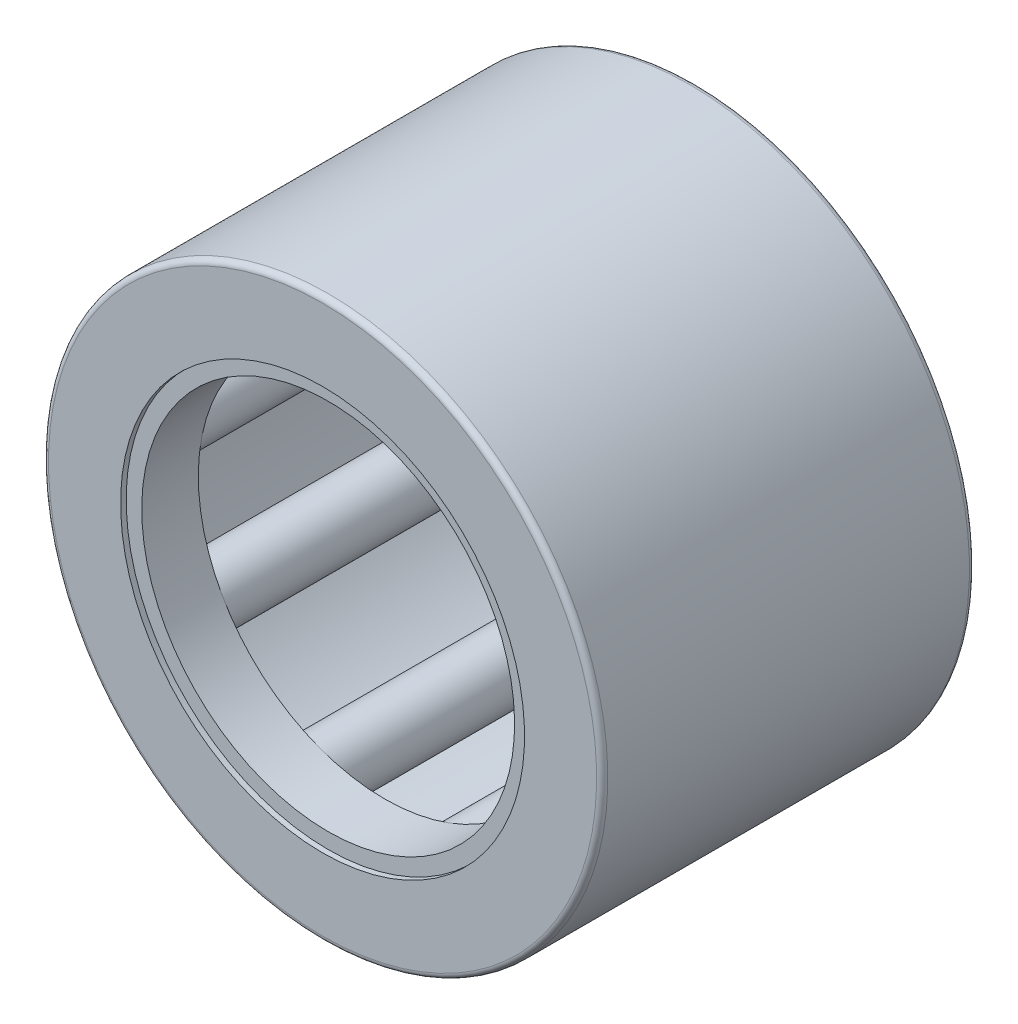
SolidWorks part; units mm, degrees
note: '?' marks a value the reader was unsure of.
ref_plane "Front Plane" through (0, 0, 0) normal (0, 0, 1) x (1, 0, 0)
ref_plane "Top Plane" through (0, 0, 0) normal (0, 1, 0) x (1, 0, 0)
ref_plane "Right Plane" through (0, 0, 0) normal (1, 0, 0) x (0, 0, -1)
sketch "Sketch1" plane through (0, 0, 0) normal (1, 0, 0) x (0, 0, -1)
  line L0 (-4, 0) -> (4, 0) construction
  line L1 (0, 0) -> (0, 6) construction
  line L2 (-4, 0) -> (-4, 6) construction
  line L3 (-4, 6) -> (4, 6)
  line L4 (4, 6) -> (4, 0) construction
  line L5 (4, 0) -> (3.3333, 0) construction
  line L6 (3.3333, 0) -> (3.3333, 5.3333) construction
  line L7 (3.3333, 5.3333) -> (-3.3333, 5.3333)
  line L8 (-3.3333, 5.3333) -> (-3.3333, 0) construction
  line L9 (-3.3333, 0) -> (-4, 0) construction
  line L10 (-4, 6) -> (-4, 4.3333)
  line L11 (-4, 4.3333) -> (-3.3333, 4.3333)
  line L12 (-3.3333, 4.3333) -> (-3.3333, 5.3333)
  line L13 (3.3333, 6) -> (3.3333, 5.3333) construction
  line L14 (3.3333, 5.3333) -> (3.3333, 4.3333)
  line L15 (3.3333, 4.3333) -> (4, 4.3333)
  line L16 (4, 4.3333) -> (4, 6)
  line L17 (3.3333, 5.3333) -> (3.3333, 4.6667) construction
  line L18 (3.3333, 4.6667) -> (3.3333, 4) construction
  line L19 (3.3333, -5.3333) -> (3.3333, -4.6667) construction
  line L20 (3.3333, -6) -> (3.3333, -5.3333) construction
  line L21 (4, -4.3333) -> (4, -6) construction
  line L22 (3.3333, -4.3333) -> (4, -4.3333) construction
  line L23 (3.3333, -5.3333) -> (3.3333, -4.3333) construction
  line L24 (-3.3333, -4.3333) -> (-3.3333, -5.3333) construction
  line L25 (-4, -4.3333) -> (-3.3333, -4.3333) construction
  line L26 (-4, -6) -> (-4, -4.3333) construction
  line L27 (3.3333, -5.3333) -> (-3.3333, -5.3333) construction
  line L28 (-4, -6) -> (4, -6) construction
  point P4 (0, 4)
  dimension "C | Width" = 8
  dimension "Fw | ID" = 8
  dimension "D | OD" = 12
sketch "Sketch7" plane through (0, 0, 0) normal (1, 0, 0) x (0, 0, -1)
  line L0 (-4, 6) -> (-4, 4.3333) construction
  line L1 (-4, 4.3333) -> (-3.3333, 4.3333) construction
  line L2 (-3.3333, 4.3333) -> (-3.3333, 5.3333) construction
  line L3 (3.3333, 5.3333) -> (-3.3333, 5.3333) construction
  line L4 (3.3333, 5.3333) -> (3.3333, 4.3333) construction
  line L5 (3.3333, 4.3333) -> (4, 4.3333) construction
  line L6 (4, 4.3333) -> (4, 6) construction
  line L8 (-4, 6) -> (4, 6) construction
  line L9 (-4, 6) -> (-4, 4.3333)
  line L10 (-4, 4.3333) -> (-3.3333, 4.3333)
  line L13 (-3.3333, 4.3333) -> (-3.3333, 5.3333)
  line L16 (3.3333, 5.3333) -> (-3.3333, 5.3333)
  line L17 (3.3333, 5.3333) -> (3.3333, 4.3333)
  line L18 (3.3333, 4.3333) -> (4, 4.3333)
  line L19 (4, 4.3333) -> (4, 6)
  line L20 (-4, 6) -> (4, 6)
revolve "Revolve1" add sketch "Sketch7" angle 360 about L0
sketch "Sketch2" plane through (0, 0, 0) normal (1, 0, 0) x (0, 0, -1)
  line L0 (-4, 4.3333) -> (-3.3333, 4.3333) construction
  line L1 (-2.6667, 4.6667) -> (2.6667, 4.6667) construction
  line L2 (-2.6667, 4.6667) -> (-2.6667, 5.3333) construction
  line L3 (-2.6667, 5.3333) -> (2.6667, 5.3333)
  line L4 (2.6667, 4.6667) -> (2.6667, 5.3333) construction
  line L5 (3.3333, 4.3333) -> (4, 4.3333) construction
  line L6 (-3.3333, 4.6667) -> (-2.6667, 4.6667) construction
  line L7 (2.6667, 4.6667) -> (3.3333, 4.6667) construction
  line L8 (4, 6) -> (4, 0) construction
  line L9 (-2.6667, 4.8333) -> (-2.6667, 4.5) construction
  line L10 (-3.3333, 4.6667) -> (-3.3333, 4.3333) construction
  line L11 (-2.6667, 5.3333) -> (-2.6667, 4.8333)
  line L12 (2.6667, 5.3333) -> (2.6667, 4.8333)
  line L13 (2.6667, 4.8333) -> (-2.6667, 4.8333)
  line L14 (0, 5.3333) -> (0, 4) construction
  line L16 (-2.6667, 4.5) -> (-3.3333, 4.5) construction
  line L17 (0, 0) -> (4, 0) construction
  line L18 (-2.6667, -4.5) -> (-3.3333, -4.5) construction
  line L19 (0, -5.3333) -> (0, -4) construction
  line L20 (-3.3333, -4.6667) -> (-3.3333, -4.3333) construction
  line L21 (-2.6667, -4.8333) -> (-2.6667, -4.5) construction
  line L22 (2.6667, -4.6667) -> (3.3333, -4.6667) construction
  line L23 (-3.3333, -4.6667) -> (-2.6667, -4.6667) construction
  line L24 (2.6667, -4.6667) -> (2.6667, -5.3333) construction
  line L25 (-2.6667, -4.6667) -> (-2.6667, -5.3333) construction
  line L26 (-2.6667, -4.6667) -> (2.6667, -4.6667) construction
  line L27 (2.6667, -4.8333) -> (-2.6667, -4.8333) construction
  line L28 (2.6667, -5.3333) -> (2.6667, -4.8333) construction
  line L29 (-2.6667, -5.3333) -> (-2.6667, -4.8333) construction
  line L30 (-2.6667, -5.3333) -> (2.6667, -5.3333) construction
  line L33 (3.3333, 5.3333) -> (-3.3333, 5.3333) construction
  line L34 (3.3333, 5.3333) -> (3.3333, 4.3333) construction
  line L35 (-3.3333, 4.3333) -> (-3.3333, 5.3333) construction
  line L36 (0, 0) -> (0, 6) construction
  point P16 (0, 4.6667)
revolve "Revolve2" add sketch "Sketch2" angle 360 about L1
sketch "Sketch3" plane through (0, 0, 0) normal (1, 0, 0) x (0, 0, -1)
  line L1 (-3.3333, 4.6667) -> (3.3333, 4.6667)
  line L2 (-3.3333, 4.6667) -> (-3.3333, 4.8333)
  line L3 (-3.3333, 4.8333) -> (3.3333, 4.8333)
  line L4 (3.3333, 4.6667) -> (3.3333, 4.8333)
  line L5 (0, 0) -> (4, 0) construction
  line L7 (3.3333, -4.6667) -> (3.3333, -4.8333) construction
  line L8 (-3.3333, -4.8333) -> (3.3333, -4.8333) construction
  line L9 (-3.3333, -4.6667) -> (-3.3333, -4.8333) construction
  line L10 (-3.3333, -4.6667) -> (3.3333, -4.6667) construction
  line L11 (3.3333, 5.3333) -> (3.3333, 4.3333) construction
  line L12 (4, 6) -> (4, 0) construction
revolve "Revolve3" add sketch "Sketch3" angle 360 about L1
ref_axis "Axis1" through (0, 4.3333, 4) along (0, 1, 0)?
pattern_circular "CirPattern1" count 9 every 40 about axis through (0, 0, 4) along (0, 0, -1) of bodies 166 167
fillet "Fillet1" radius 0.12 2 edges at (0, -6, -4) (0, -6, 4)
sketch "Sketch4" plane through (0, 0, 0) normal (1, 0, 0) x (0, 0, -1)
  line L0 (2.6667, 5.3333) -> (2.6667, 4.8333) construction
  line L1 (3.88, 4) -> (2.6667, 4)
  line L2 (3.88, 4) -> (3.88, 4.3333)
  line L3 (3.88, 4.3333) -> (2.6667, 4.3333)
  line L4 (2.6667, 4) -> (2.6667, 4.3333)
  line L7 (3.3333, 4.3333) -> (4, 4.3333) construction
  line L8 (3.88, -6) -> (3.88, 6) construction
revolve "Revolve4" add sketch "Sketch4" angle 360 about L0
sketch "Sketch5" plane through (0, 0, 0) normal (1, 0, 0) x (0, 0, -1)
  line L0 (-3.88, 6) -> (-3.88, -6) construction
  line L1 (-2.6667, 4) -> (-3.88, 4)
  line L2 (-2.6667, 4) -> (-2.6667, 4.3333)
  line L3 (-2.6667, 4.3333) -> (-3.88, 4.3333)
  line L4 (-3.88, 4) -> (-3.88, 4.3333)
  line L5 (-2.6667, 5.3333) -> (-2.6667, 4.8333) construction
  line L6 (-4, 4.3333) -> (-3.3333, 4.3333) construction
revolve "Revolve5" add sketch "Sketch5" angle 360 about L0
sketch "Front View" plane through (0, 0, 0) normal (0, 0, 1) x (1, 0, 0)
  circle A0 centre (0, 0) radius 4 construction
  circle A1 centre (0, 0) radius 6 construction
  dimension "ID" = 8
  dimension "OD" = 12
sketch "Right View" plane through (0, 0, 0) normal (1, 0, 0) x (0, 0, -1)
  line L0 (-4, 6) -> (4, 6) construction
  line L1 (-4, 6) -> (4, 6) construction
  line L2 (0, 0) -> (0, 6) construction
  point P4 (0, 6)
  dimension "Width" = 8
equation "\"Rollers@CirPattern1\"  = \"OD@Sketch1\"*.75"
equation "\"D1@Fillet1\" = \"D | OD@Sketch1\" * .01"
equation "\"Angle@CirPattern1\"=360 / \"Rollers@CirPattern1\""
equation "\"ID@Front View\" = \"Fw | ID@Sketch1\""
equation "\"OD@Front View\" = \"D | OD@Sketch1\""
equation "\"Width@Right View\" = \"C | Width@Sketch1\""
